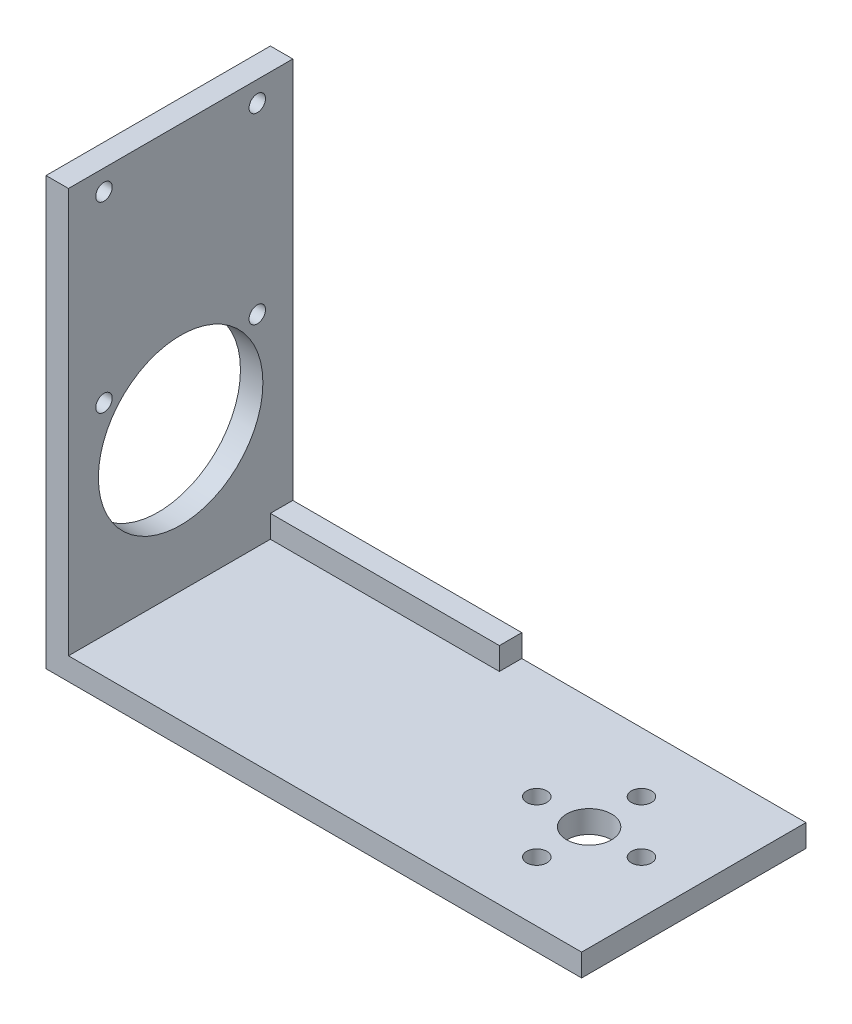
SolidWorks part; units mm, degrees
ref_plane "Front Plane" through (0, 0, 0) normal (0, 0, 1) x (1, 0, 0)
ref_plane "Top Plane" through (0, 0, 0) normal (0, 1, 0) x (1, 0, 0)
ref_plane "Right Plane" through (0, 0, 0) normal (1, 0, 0) x (0, 0, -1)
ref_plane "PZ_m15_000" through (0, 0, -15) normal (0, 0, 1) x (1, 0, 0)
sketch "S_box1" plane through (0, 0, -15) normal (0, 0, 1) x (1, 0, 0)
  line L0 (-57.625, -21.625) -> (14, -21.625)
  line L1 (14, -21.625) -> (14, -18.625)
  line L2 (14, -18.625) -> (-57.625, -18.625)
  line L3 (-57.625, -18.625) -> (-57.625, -21.625)
  dimension "P1" = 57.625
  dimension "P2" = 21.625
  dimension "P3" = 14
  dimension "P4" = 21.625
  dimension "P5" = 14
  dimension "P6" = 18.625
  dimension "P7" = 57.625
  dimension "P8" = 18.625
extrude "Boss_1" add sketch "S_box1" along normal blind 30
sketch "S_box2" plane through (0, 0, -15) normal (0, 0, 1) x (1, 0, 0)
  line L0 (-57.625, -19.125) -> (-54.625, -19.125)
  line L1 (-54.625, -19.125) -> (-54.625, 35.5)
  line L2 (-54.625, 35.5) -> (-57.625, 35.5)
  line L3 (-57.625, 35.5) -> (-57.625, -19.125)
  dimension "P1" = 57.625
  dimension "P2" = 19.125
  dimension "P3" = 54.625
  dimension "P4" = 19.125
  dimension "P5" = 54.625
  dimension "P6" = 35.5
  dimension "P7" = 57.625
  dimension "P8" = 35.5
extrude "Boss_2" add sketch "S_box2" along normal blind 30
sketch "S_box3" plane through (0, 0, -15) normal (0, 0, 1) x (1, 0, 0)
  line L0 (-55.125, -19.125) -> (-24, -19.125)
  line L1 (-24, -19.125) -> (-24, -15.625)
  line L2 (-24, -15.625) -> (-55.125, -15.625)
  line L3 (-55.125, -15.625) -> (-55.125, -19.125)
  dimension "P1" = 55.125
  dimension "P2" = 19.125
  dimension "P3" = 24
  dimension "P4" = 19.125
  dimension "P5" = 24
  dimension "P6" = 15.625
  dimension "P7" = 55.125
  dimension "P8" = 15.625
extrude "Boss_3" add sketch "S_box3" along normal blind 3
ref_plane "PY_m21_725" through (0, -21.725, 0) normal (0, 1, 0) x (1, 0, 0)
sketch "S_hole4" plane through (0, -21.725, 0) normal (0, 1, 0) x (1, 0, 0)
  circle A0 centre (0, 0) radius 3
  dimension "D1_S_hole4" = 6
extrude "Hole_4" cut sketch "S_hole4" along normal blind 3.2
sketch "S_hole5" plane through (0, -21.725, 0) normal (0, 1, 0) x (1, 0, 0)
  circle A0 centre (7, 0) radius 1.35
  dimension "D1_S_hole5" = 2.7
  dimension "P2" = 7
extrude "Hole_5" cut sketch "S_hole5" along normal blind 3.2
sketch "S_hole6" plane through (0, -21.725, 0) normal (0, 1, 0) x (1, 0, 0)
  circle A0 centre (0, -7) radius 1.35
  dimension "D1_S_hole6" = 2.7
  dimension "P2" = 7
extrude "Hole_6" cut sketch "S_hole6" along normal blind 3.2
sketch "S_hole7" plane through (0, -21.725, 0) normal (0, 1, 0) x (1, 0, 0)
  circle A0 centre (-7, 0) radius 1.35
  dimension "D1_S_hole7" = 2.7
  dimension "P2" = 7
extrude "Hole_7" cut sketch "S_hole7" along normal blind 3.2
sketch "S_hole8" plane through (0, -21.725, 0) normal (0, 1, 0) x (1, 0, 0)
  circle A0 centre (0, 7) radius 1.35
  dimension "D1_S_hole8" = 2.7
  dimension "P2" = 7
extrude "Hole_8" cut sketch "S_hole8" along normal blind 3.2
ref_plane "PX_m57_725" through (-57.725, 0, 0) normal (1, 0, 0) x (0, 0, -1)
sketch "S_hole9" plane through (-57.725, 0, 0) normal (1, 0, 0) x (0, 0, -1)
  circle A0 centre (0, 0) radius 11
  dimension "D1_S_hole9" = 22
extrude "Hole_9" cut sketch "S_hole9" along normal blind 3.2
sketch "S_hole10" plane through (-57.725, 0, 0) normal (1, 0, 0) x (0, 0, -1)
  circle A0 centre (10.25, 8.3) radius 1.1
  dimension "D1_S_hole10" = 2.2
  dimension "P2" = 10.25
  dimension "P3" = 8.3
extrude "Hole_10" cut sketch "S_hole10" along normal blind 3.2
sketch "S_hole11" plane through (-57.725, 0, 0) normal (1, 0, 0) x (0, 0, -1)
  circle A0 centre (-10.25, 8.3) radius 1.1
  dimension "D1_S_hole11" = 2.2
  dimension "P2" = 10.25
  dimension "P3" = 8.3
extrude "Hole_11" cut sketch "S_hole11" along normal blind 3.2
sketch "S_hole12" plane through (-57.725, 0, 0) normal (1, 0, 0) x (0, 0, -1)
  circle A0 centre (10.25, 32.75) radius 1.1
  dimension "D1_S_hole12" = 2.2
  dimension "P2" = 10.25
  dimension "P3" = 32.75
extrude "Hole_12" cut sketch "S_hole12" along normal blind 3.2
sketch "S_hole13" plane through (-57.725, 0, 0) normal (1, 0, 0) x (0, 0, -1)
  circle A0 centre (-10.25, 32.75) radius 1.1
  dimension "D1_S_hole13" = 2.2
  dimension "P2" = 10.25
  dimension "P3" = 32.75
extrude "Hole_13" cut sketch "S_hole13" along normal blind 3.2
equation "\"plate_t\" = 3"
equation "\"clearance\" = 0.4"
